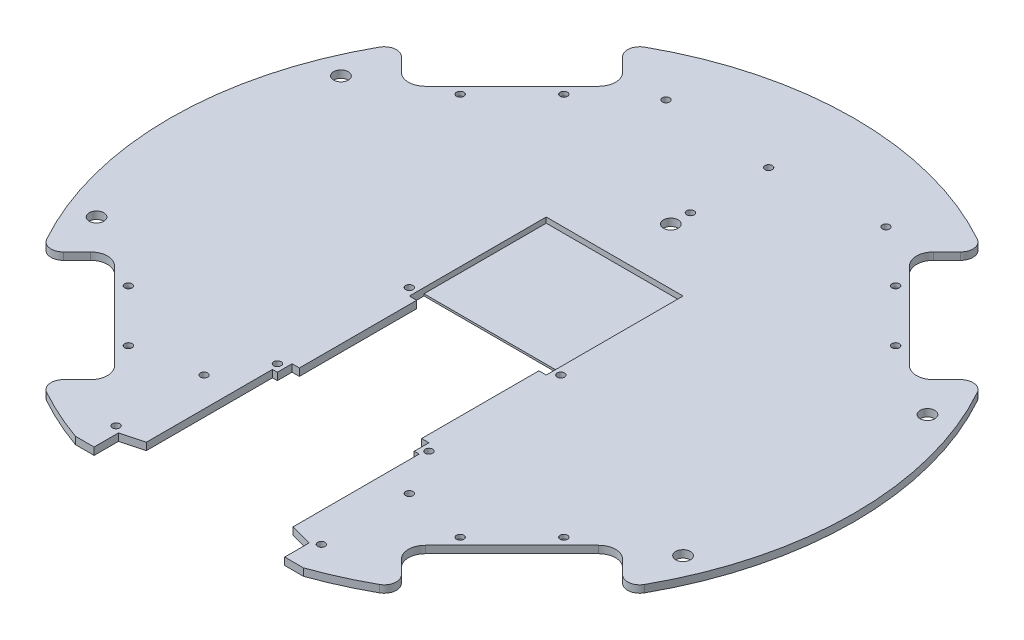
SolidWorks part; units mm, degrees
material "1060 Alloy"
ref_plane "Front Plane" through (0, 0, 0) normal (0, 0, 1) x (1, 0, 0)
ref_plane "Top Plane" through (0, 0, 0) normal (0, 1, 0) x (1, 0, 0)
ref_plane "Right Plane" through (0, 0, 0) normal (1, 0, 0) x (0, 0, -1)
sketch "Sketch1" plane through (0, 0, 0) normal (0, 1, 0) x (1, 0, 0)
  circle A0 centre (0, 0) radius 140
  dimension "D1" = 280
extrude "Boss-Extrude1" add sketch "Sketch1" along normal blind 3
sketch "Sketch7" plane through (0, 3, 0) normal (0, 1, 0) x (1, 0, 0)
  line L0 (-99.0303, -63.6043) -> (-63.6043, -99.0303)
  line L1 (-108.8591, -63.6043) -> (-121.6224, -76.3675)
  line L2 (-63.6043, -108.8591) -> (-76.3675, -121.6224)
  line L3 (-121.6224, -76.3675) -> (-76.3675, -121.6224)
  line L4 (0, 0) -> (-98.9949, -98.9949) construction
  line L7 (0, 0) -> (0, 130) construction
  circle A0 centre (0, 0) radius 140 construction
  arc A1 (-108.8591, -63.6043) -> (-99.0303, -63.6043) centre (-103.9447, -68.5186) cw
  arc A2 (-63.6043, -99.0303) -> (-63.6043, -108.8591) centre (-68.5186, -103.9447) cw
  dimension "D4" = 6.95
  dimension "D1" = 115
  dimension "D2" = 64
  dimension "D3" = 135
extrude "Cut-Extrude4" cut sketch "Sketch7" against normal up to next
sketch "Sketch9" plane through (0, 3, 0) normal (0, 1, 0) x (1, 0, 0)
  line L1 (-63.6043, -99.0303) -> (-99.0303, -63.6043) construction
  line L4 (-108.8591, -63.6043) -> (-119.0017, -73.7469) construction
  circle A0 centre (-89.0955, -67.8823) radius 1.5
  circle A1 centre (-67.8823, -89.0955) radius 1.5
  dimension "D4" = 3
  dimension "D1" = 4
  dimension "D2" = 30
  dimension "D3" = 17
  dimension "D5" = 4
extrude "Cut-Extrude6" cut sketch "Sketch9" against normal up to next
fillet "Fillet1" radius 5 2 edges at (-73.7469, 1.5, 119.0017) (-119.0017, 1.5, 73.7469)
pattern_circular "CirPattern1" count 4 over 360 about axis through (0, 3, 0) along (0, 1, 0) of "Cut-Extrude4", "Fillet1", "Cut-Extrude6"
sketch "Sketch2" plane through (0, 3, 0) normal (0, 1, 0) x (1, 0, 0)
  line L0 (-46.6476, -132) -> (-39, -132)
  line L1 (-30, -119.5885) -> (-30, -68)
  line L2 (-28, -8) -> (28, -8)
  line L3 (30, -68) -> (30, -119.5885)
  line L4 (39, -132) -> (46.6476, -132)
  line L5 (46.6476, -132) -> (46.6476, -140)
  line L6 (46.6476, -140) -> (-46.6476, -140)
  line L7 (-46.6476, -140) -> (-46.6476, -132)
  line L8 (-28, -62) -> (-28, -68)
  line L9 (-28, -68) -> (-30, -68)
  line L10 (28, -62) -> (28, -68)
  line L11 (28, -68) -> (30, -68)
  line L12 (-28, -62) -> (-25, -62)
  line L13 (-25, -62) -> (-25, -14)
  line L14 (-25, -14) -> (-28, -14)
  line L15 (-28, -14) -> (-28, -8)
  line L16 (28, -8) -> (28, -14)
  line L17 (28, -14) -> (25, -14)
  line L18 (25, -14) -> (25, -62)
  line L19 (25, -62) -> (28, -62)
  line L20 (-39, -132) -> (-39, -122)
  line L21 (-39, -122) -> (-30, -119.5885)
  line L22 (39, -132) -> (39, -122)
  line L23 (39, -122) -> (30, -119.5885)
  circle A0 centre (0, 0) radius 140 construction
  dimension "D8" = 3
  dimension "D5" = 60
  dimension "D6" = 56
  dimension "D1" = 8
  dimension "D2" = 124
  dimension "D3" = 60
  dimension "D4" = 16.6476
  dimension "D7" = 6
  dimension "D9" = 78
  dimension "D10" = 10
  dimension "D11" = 105
extrude "Cut-Extrude1" cut sketch "Sketch2" against normal up to next
fillet "Fillet3" radius 1.5 8 edges at (67.8823, 0, 90.5955) (89.0955, 0, 69.3823) (89.0955, 0, -66.3823) (67.8823, 0, -87.5955) (-67.8823, 0, -87.5955) (-89.0955, 0, -66.3823) (-67.8823, 0, 90.5955) (-89.0955, 0, 69.3823)
sketch "Sketch10" plane through (0, 3, 0) normal (0, 1, 0) x (1, 0, 0)
  circle A0 centre (-31, -65) radius 1.5
  circle A1 centre (31, -65) radius 1.5
  circle A2 centre (-31, -11) radius 1.5
  circle A3 centre (31, -11) radius 1.5
  dimension "D3" = 3
  dimension "D1" = 31
  dimension "D2" = 62
  dimension "D4" = 65
  dimension "D5" = 54
extrude "Cut-Extrude7" cut sketch "Sketch10" against normal up to next
sketch "Sketch13" plane through (0, 3, 0) normal (0, 1, 0) x (1, 0, 0)
  line L1 (-39, -132) -> (-46.6476, -132) construction
  circle A0 centre (-42, -84) radius 1.5
  circle A1 centre (-42, -120) radius 1.5
  circle A2 centre (42, -120) radius 1.5
  circle A3 centre (42, -84) radius 1.5
  dimension "D1" = 3
  dimension "D2" = 12
  dimension "D3" = 36
  dimension "D4" = 42
  dimension "D5" = 42
extrude "Cut-Extrude9" cut sketch "Sketch13" against normal up to next
sketch "Sketch16" plane through (0, 3, 0) normal (0, 1, 0) x (1, 0, 0)
  circle A0 centre (0, 73) radius 1.5
  circle A1 centre (-45, 108) radius 1.5
  circle A2 centre (45, 108) radius 1.5
  circle A3 centre (0, 105) radius 1.5
  circle A4 centre (0, 65) radius 3
  dimension "D2" = 3
  dimension "D5" = 6
  dimension "D1" = 73
  dimension "D3" = 108
  dimension "D4" = 90
  dimension "D6" = 32
  dimension "D7" = 65
extrude "Cut-Extrude12" cut sketch "Sketch16" against normal up to next
sketch "Sketch17" plane through (0, 3, 0) normal (0, 1, 0) x (1, 0, 0)
  circle A0 centre (-120, 50) radius 3
  circle A1 centre (-120, -50) radius 3
  circle A2 centre (120, 50) radius 3
  circle A3 centre (120, -50) radius 3
  dimension "D1" = 6
  dimension "D2" = 50
  dimension "D3" = 50
  dimension "D4" = 120
  dimension "D5" = 120
extrude "Cut-Extrude13" cut sketch "Sketch17" against normal up to next
sketch "Sketch18" plane through (0, 3, 0) normal (0, 1, 0) x (1, 0, 0)
  line L0 (-28, -8) -> (-28, -14) construction
  line L1 (-28, -8) -> (28, -8)
  line L2 (-28, -8) -> (-28, 42)
  line L3 (-28, 42) -> (28, 42)
  line L4 (28, -8) -> (28, 42)
  line L5 (28, -8) -> (-28, -8) construction
  line L6 (28, -8) -> (-28, -8) construction
  dimension "D1" = 50
extrude "Cut-Extrude14" cut sketch "Sketch18" against normal blind 2.2
